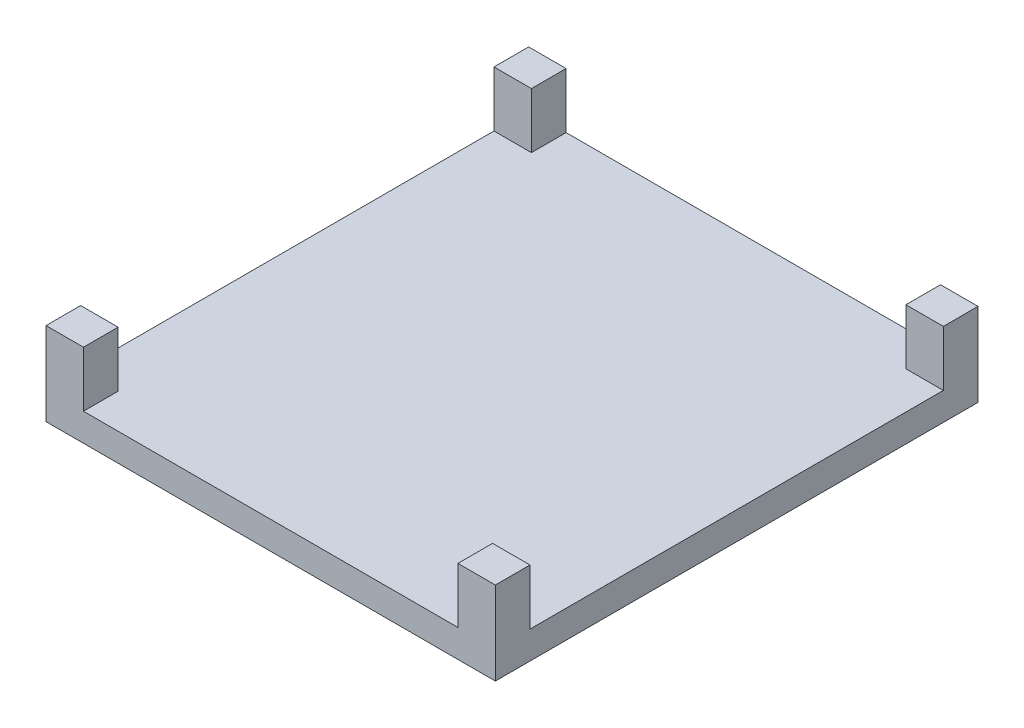
SolidWorks part; units mm, degrees
ref_plane "Front Plane" through (0, 0, 0) normal (0, 0, 1) x (1, 0, 0)
ref_plane "Top Plane" through (0, 0, 0) normal (0, 1, 0) x (1, 0, 0)
ref_plane "Right Plane" through (0, 0, 0) normal (1, 0, 0) x (0, 0, -1)
sketch "Sketch1" plane through (0, 0, 0) normal (0, 1, 0) x (1, 0, 0)
  line L0 (0, -44.45) -> (0, 44.45) construction
  line L1 (-41.275, 44.45) -> (41.275, 44.45)
  line L2 (-41.275, 44.45) -> (-41.275, -44.45)
  line L3 (-41.275, -44.45) -> (41.275, -44.45)
  line L4 (41.275, 44.45) -> (41.275, -44.45)
  line L5 (-41.275, 44.45) -> (41.275, -44.45) construction
  line L6 (-41.275, -44.45) -> (41.275, 44.45) construction
  line L7 (-41.275, 0) -> (41.275, 0) construction
  circle A0 centre (38.1, -41.275) radius 2.3812
  circle A1 centre (-38.1, -41.275) radius 2.3812
  circle A2 centre (38.1, 41.275) radius 2.3812
  circle A3 centre (-38.1, 41.275) radius 2.3812
  point P0 (0, 0)
  dimension "D3" = 76.2
  dimension "D5" = 38.1
  dimension "D6" = 3.175
  dimension "D1" = 88.9
  dimension "D2" = 82.55
  dimension "D4" = 82.55
sketch "Sketch2" plane through (0, 0, 0) normal (0, 1, 0) x (1, 0, 0)
  line L0 (0, -44.196) -> (0, 44.196) construction
  line L1 (-41.148, 44.196) -> (41.148, 44.196)
  line L2 (-41.148, 44.196) -> (-41.148, -44.196)
  line L3 (-41.148, -44.196) -> (41.148, -44.196)
  line L4 (41.148, 44.196) -> (41.148, -44.196)
  line L5 (-41.148, 44.196) -> (41.148, -44.196) construction
  line L6 (-41.148, -44.196) -> (41.148, 44.196) construction
  line L7 (-41.148, 0) -> (41.148, 0) construction
  circle A0 centre (37.719, -41.021) radius 1.778
  circle A1 centre (-37.719, -41.021) radius 1.778
  circle A2 centre (37.719, 41.021) radius 1.778
  circle A3 centre (-37.719, 41.021) radius 1.778
  point P0 (0, 0)
  dimension "D3" = 75.438
  dimension "D5" = 37.719
  dimension "D6" = 3.429
  dimension "D9" = 3.556
  dimension "D10" = 3.556
  dimension "D11" = 3.556
  dimension "D12" = 3.556
  dimension "D1" = 88.392
  dimension "D2" = 82.296
  dimension "D4" = 82.042
  dimension "D13" = 3.429
  dimension "D14" = 3.175
  dimension "D15" = 3.429
  dimension "D16" = 3.175
  dimension "D17" = 3.429
  dimension "D18" = 3.175
extrude "Boss-Extrude3" add sketch "Sketch2<4>" along normal blind 5.08 contours L2 L1 L4 L3
sketch "Sketch2<4>" plane through (0, 0, 0) normal (0, 1, 0) x (1, 0, 0) same geometry as "Sketch2"
sketch "Sketch5" plane through (0, 5.08, 0) normal (0, 1, 0) x (1, 0, 0)
  line L0 (-41.148, 44.196) -> (-41.148, -44.196) construction
  line L5 (-34.29, -44.196) -> (-34.29, -37.846)
  line L6 (-34.29, 37.846) -> (-41.148, 37.846)
  line L7 (41.148, 44.196) -> (41.148, -44.196) construction
  line L8 (-34.29, 37.846) -> (-34.29, 44.196)
  line L9 (-34.29, 44.196) -> (-41.148, 44.196)
  line L10 (-41.148, 37.846) -> (-41.148, 44.196)
  line L11 (-34.29, 37.846) -> (-41.148, 44.196) construction
  line L12 (-34.29, 44.196) -> (-41.148, 37.846) construction
  line L13 (-34.29, -44.196) -> (-41.148, -44.196)
  line L14 (-41.148, -44.196) -> (-41.148, -37.846)
  line L15 (-34.29, -37.846) -> (-41.148, -37.846)
  line L16 (0, 44.196) -> (0, -44.196) construction
  line L17 (-41.148, 44.196) -> (41.148, 44.196) construction
  line L18 (34.29, -44.196) -> (41.148, -44.196)
  line L19 (41.148, -44.196) -> (41.148, -37.846)
  line L20 (34.29, -37.846) -> (41.148, -37.846)
  line L21 (34.29, -44.196) -> (34.29, -37.846)
  line L22 (34.29, 44.196) -> (41.148, 44.196)
  line L23 (41.148, 37.846) -> (41.148, 44.196)
  line L24 (34.29, 37.846) -> (41.148, 37.846)
  line L25 (34.29, 37.846) -> (34.29, 44.196)
  point P0 (-37.719, 41.021)
  point P35 (37.973, 41.021)
  point P38 (37.973, 41.021)
  point P49 (-37.719, -41.021)
  point P52 (-37.719, -41.021)
  point P63 (37.973, -41.021)
  point P66 (37.973, -41.021)
  dimension "D1" = 6.35
  dimension "D2" = 6.858
  dimension "D5" = 82.042
  dimension "D6" = 2
  dimension "D3" = 82.296
  dimension "D4" = 75.692
extrude "Boss-Extrude4" add sketch "Sketch5" along normal blind 10.16
